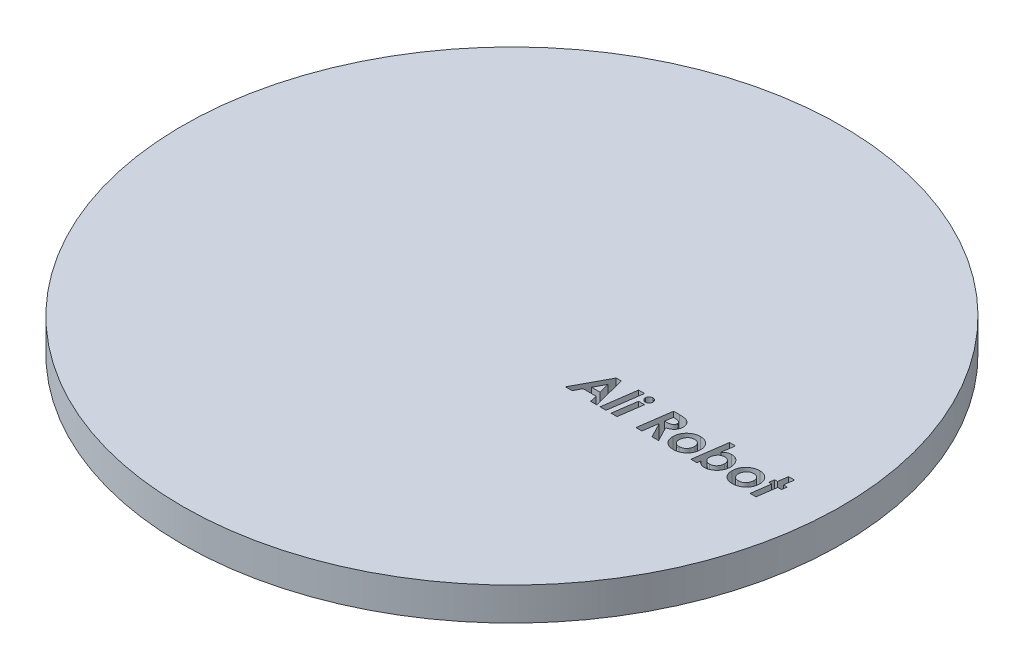
SolidWorks part; units mm, degrees
ref_plane "Front Plane" through (0, 0, 0) normal (0, 0, 1) x (1, 0, 0)
ref_plane "Top Plane" through (0, 0, 0) normal (0, 1, 0) x (1, 0, 0)
ref_plane "Right Plane" through (0, 0, 0) normal (1, 0, 0) x (0, 0, -1)
sketch "Sketch2" plane through (0, 0, 0) normal (0, 1, 0) x (1, 0, 0)
  circle A0 centre (0, 0) radius 35
  dimension "D1" = 70
extrude "Boss-Extrude1" add sketch "Sketch2" along normal blind 3.5
ref_plane "Plane1" through (-4, 0, 0) normal (1, 0, 0) x (0, 0, -1)
sketch "Sketch7" plane through (-4, 0, 0) normal (1, 0, 0) x (0, 0, -1)
  line L0 (18.6521, 16.3561) -> (18.6521, 3.5)
  line L5 (35, 3.5) -> (-35, 3.5) construction
  line L6 (-22.6311, 24.9401) -> (3.3119, 50.8831)
  line L7 (-43.5609, 3.5) -> (18.6521, 3.5)
  line L11 (-29.9535, 3.5) -> (-29.9535, 7.2624)
  arc A4 (24.252, 29.4036) -> (3.3119, 50.8831) centre (13.9185, 40.2765) ccw
  arc A5 (24.252, 29.4036) -> (18.6521, 16.3561) centre (36.6521, 16.3561) ccw
  arc A6 (-22.6311, 24.9401) -> (-29.9535, 7.2624) centre (-4.9535, 7.2624) ccw
  dimension "D1" = 25
  dimension "D4" = 30
  dimension "D3" = 18
  dimension "D5" = 45
sketch "Sketch33" plane through (0, 0, 0) normal (0, -1, 0) x (1, 0, 0)
  circle A0 centre (0, 0) radius 30
  dimension "D1" = 60
extrude "Boss-Extrude3" add sketch "Sketch33" along normal blind 2.2
ref_plane "Plane2" through (0, -4.2, 0) normal (0, -1, 0) x (-1, 0, 0)
sketch "Sketch35" plane through (64.9204, -4.2, -6.6124) normal (0, 1, 0) x (1, 0, 0)
  line L0 (-64.9204, 23.3876) -> (-64.9204, -51.1324) construction
  line L1 (-64.9204, -6.5857) -> (-104.2271, -6.5857) construction
  line L3 (-62.0204, -8.2857) -> (-67.8204, -8.2857)
  line L4 (-62.0204, -8.2857) -> (-62.0204, -4.8857)
  line L5 (-62.0204, -4.8857) -> (-67.8204, -4.8857)
  line L6 (-67.8204, -8.2857) -> (-67.8204, -4.8857)
  circle A0 centre (-64.9204, -6.6124) radius 30 construction
  circle A1 centre (-64.9204, -6.6124) radius 30 construction
  dimension "D1" = 3.4
  dimension "D2" = 5.8
  dimension "D3" = 1.7
  dimension "D4" = 2.9
sketch "Sketch38" plane through (0, 3.5, 0) normal (0, 1, 0) x (1, 0, 0)
  text T0 "<b><i>Ali Robot</i></b>"
extrude "Cut-Extrude24" cut sketch "Sketch38" against normal blind 3
extrude "Boss-Extrude4" add sketch "Sketch35" against normal blind 6
shell "Shell2" thickness 1 removed face at (0, -10.2, -0.0268) outward yes
sketch "Sketch39" plane through (0, -2.2, 0) normal (0, -1, 0) x (-1, 0, 0)
  circle A0 centre (0, 0) radius 4.25
  circle A1 centre (0, 0) radius 5.5
extrude "Boss-Extrude5" add sketch "Sketch39" along normal blind 9
sketch "Sketch40" plane through (0, -10.2, 0) normal (0, -1, 0) x (-1, 0, 0)
  line L0 (-3.9, 0) -> (5.8228, 0.0268) construction
  line L1 (-3.9, -1.6889) -> (-3.9, 1.6889) construction
  line L2 (0, 0.0268) -> (39.3067, 0.0268) construction
sketch "Sketch41" plane through (0, -10.2, 0) normal (0, -1, 0) x (-1, 0, 0)
  line L0 (0, 1.7268) -> (0, -7.344) construction
  line L1 (-2.9, 1.7268) -> (2.9, 1.7268) construction
  circle A0 centre (0, 0) radius 3.7
  circle A1 centre (0, 0) radius 4.5
extrude "Boss-Extrude6" add sketch "Sketch41" along normal blind 4
